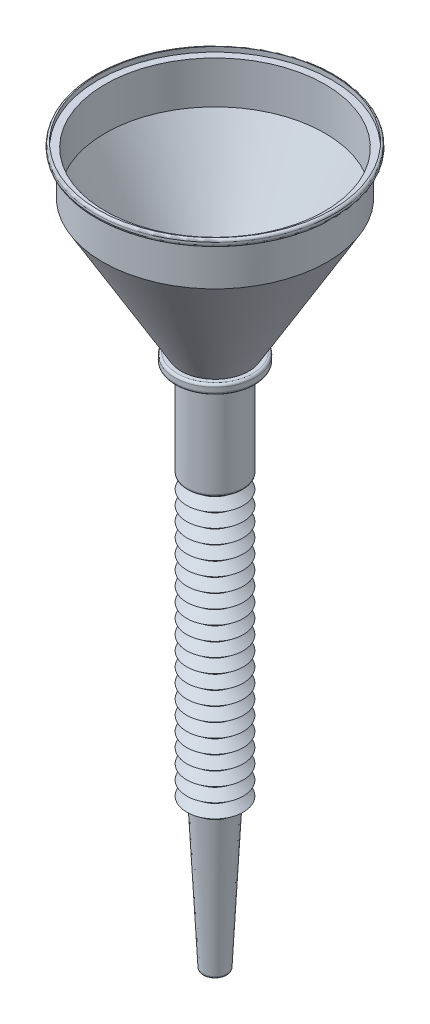
SolidWorks part; units mm, degrees
material "PE Low/Medium Density"
ref_plane "Front Plane" through (0, 0, 0) normal (0, 0, 1) x (1, 0, 0)
ref_plane "Top Plane" through (0, 0, 0) normal (0, 1, 0) x (1, 0, 0)
ref_plane "Right Plane" through (0, 0, 0) normal (1, 0, 0) x (0, 0, -1)
sketch "Sketch1" plane through (0, 0, 0) normal (0, 0, 1) x (1, 0, 0)
  line L0 (0, 0) -> (0, 139.1915) construction
  line L1 (0, 0) -> (63.5, 0)
  line L2 (63.5, 0) -> (63.5, -3.81)
  line L3 (59.69, -25.4) -> (17.9793, -96.52)
  line L5 (63.5, -3.81) -> (59.69, -3.81)
  line L6 (59.69, -3.81) -> (59.69, -25.4)
  line L7 (15, -101.6) -> (15, -152.4)
  line L8 (0, 0) -> (0, -381)
  line L9 (10.16, -304.8) -> (6.35, -381)
  line L10 (6.35, -381) -> (0, -381)
  line L11 (15, -152.4) -> (10.16, -152.4)
  line L12 (10.16, -152.4) -> (10.16, -304.8)
  line L13 (17.9793, -96.52) -> (21.35, -96.52)
  line L14 (21.35, -96.52) -> (21.35, -101.6)
  line L15 (21.35, -101.6) -> (15, -101.6)
  line L16 (17.9793, -96.52) -> (15, -101.6) construction
  point P4 (0, 0)
  dimension "D1" = 127
  dimension "D2" = 30
  dimension "D3" = 25.4
  dimension "D4" = 3.81
  dimension "D5" = 3.81
  dimension "D6" = 101.6
  dimension "D7" = 12.7
  dimension "D8" = 76.2
  dimension "D9" = 381
  dimension "D10" = 20.32
  dimension "D11" = 50.8
  dimension "D12" = 5.08
  dimension "D13" = 6.35
revolve "Revolve1" add sketch "Sketch1" angle 360 about L0
sketch "Sketch3" plane through (0, 0, 0) normal (0, 0, 1) x (1, 0, 0)
  line L0 (15, -152.4) -> (10.16, -156.1171)
  line L1 (10.16, -304.8) -> (10.16, -152.4) construction
  line L2 (10.16, -156.1171) -> (15, -159.8341)
  line L3 (15, -152.4) -> (0, -152.4)
  line L4 (-10.16, -152.4) -> (10.16, -152.4) construction
  line L5 (0, -152.4) -> (0, -304.8)
  line L6 (10.16, -304.8) -> (-10.16, -304.8) construction
  line L7 (0, -304.8) -> (10.16, -304.8)
  line L8 (6.35, -381) -> (10.16, -304.8) construction
  line L9 (10.16, -163.5512) -> (15, -167.2683)
  line L10 (15, -159.8341) -> (10.16, -163.5512)
  line L11 (10.16, -170.9854) -> (15, -174.7024)
  line L12 (15, -167.2683) -> (10.16, -170.9854)
  line L13 (10.16, -178.4195) -> (15, -182.1366)
  line L14 (15, -174.7024) -> (10.16, -178.4195)
  line L15 (10.16, -185.8537) -> (15, -189.5707)
  line L16 (15, -182.1366) -> (10.16, -185.8537)
  line L17 (10.16, -193.2878) -> (15, -197.0049)
  line L18 (15, -189.5707) -> (10.16, -193.2878)
  line L19 (10.16, -200.722) -> (15, -204.439)
  line L20 (15, -197.0049) -> (10.16, -200.722)
  line L21 (10.16, -208.1561) -> (15, -211.8732)
  line L22 (15, -204.439) -> (10.16, -208.1561)
  line L23 (10.16, -215.5902) -> (15, -219.3073)
  line L24 (15, -211.8732) -> (10.16, -215.5902)
  line L25 (10.16, -223.0244) -> (15, -226.7415)
  line L26 (15, -219.3073) -> (10.16, -223.0244)
  line L27 (10.16, -230.4585) -> (15, -234.1756)
  line L28 (15, -226.7415) -> (10.16, -230.4585)
  line L29 (10.16, -237.8927) -> (15, -241.6098)
  line L30 (15, -234.1756) -> (10.16, -237.8927)
  line L31 (10.16, -245.3268) -> (15, -249.0439)
  line L32 (15, -241.6098) -> (10.16, -245.3268)
  line L33 (10.16, -252.761) -> (15, -256.478)
  line L34 (15, -249.0439) -> (10.16, -252.761)
  line L35 (10.16, -260.1951) -> (15, -263.9122)
  line L36 (15, -256.478) -> (10.16, -260.1951)
  line L37 (10.16, -267.6293) -> (15, -271.3463)
  line L38 (15, -263.9122) -> (10.16, -267.6293)
  line L39 (10.16, -275.0634) -> (15, -278.7805)
  line L40 (15, -271.3463) -> (10.16, -275.0634)
  line L41 (10.16, -282.4976) -> (15, -286.2146)
  line L42 (15, -278.7805) -> (10.16, -282.4976)
  line L43 (10.16, -289.9317) -> (15, -293.6488)
  line L44 (15, -286.2146) -> (10.16, -289.9317)
  line L45 (10.16, -297.3659) -> (15, -301.0829)
  line L46 (15, -293.6488) -> (10.16, -297.3659)
  line L47 (15, -152.4) -> (15, -101.6) construction
  line L48 (15, -301.0829) -> (10.16, -304.8)
  line L49 (10.16, -304.8) -> (15, -308.5171) [skipped]
  point P6 (30, -152.4)
  point P16 (19.05, -289.2336)
  point P19 (30, -152.4)
  point P22 (29.4786, -152.4)
  point P74 (30, -159.1808)
  dimension "D3" = 21
revolve "Revolve2" add sketch "Sketch3" angle 360 about L5
shell "Shell1" thickness 1.27 removed face at (0, -381, -6.35) removed face at (0, 0, -63.5)
fillet "Fillet1" radius 1.27 7 edges at (0, -101.6, -15) (0, -152.4, -15) (0, -381, -6.35) (0, -3.81, -63.5) (0, 0, -63.5) (0, -96.52, -21.35) (0, -101.6, -21.35)
